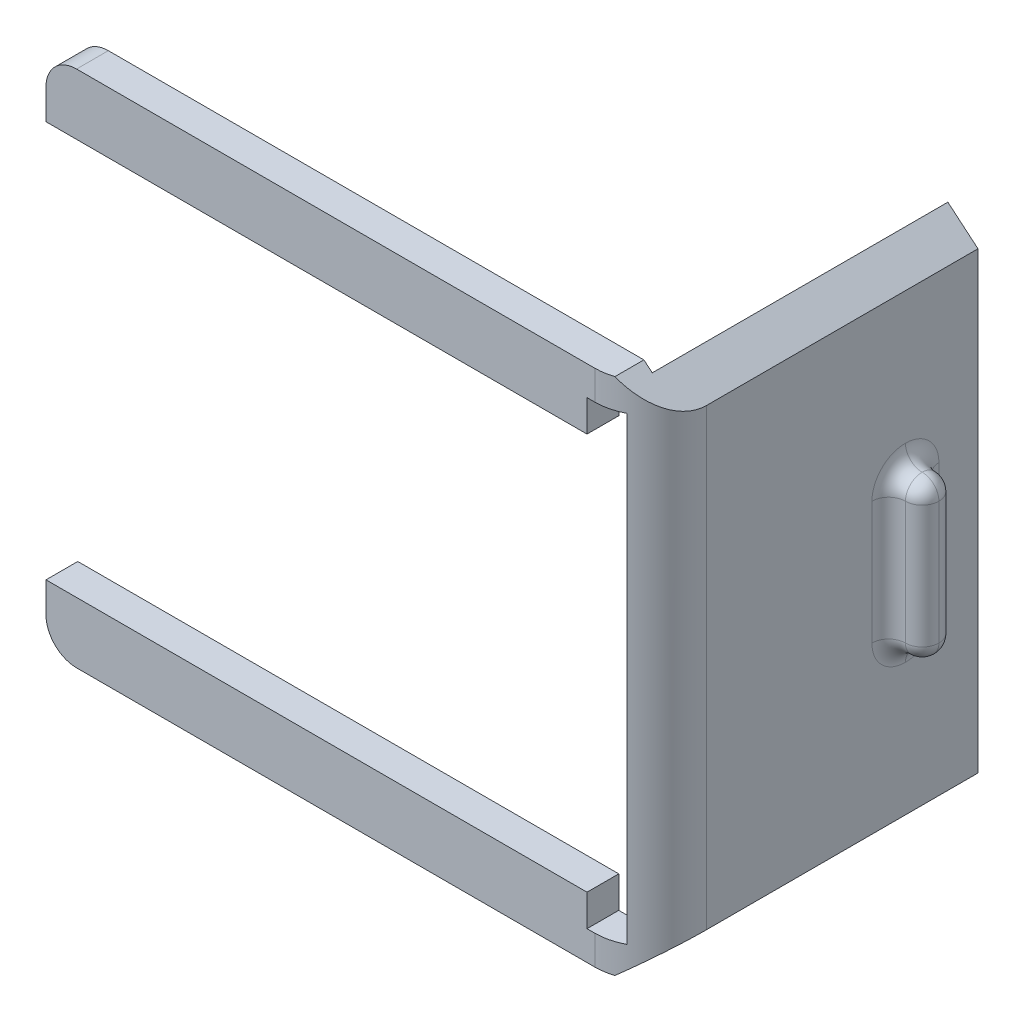
SolidWorks part; units mm, degrees
ref_plane "Front Plane" through (0, 0, 0) normal (0, 0, 1) x (1, 0, 0)
ref_plane "Top Plane" through (0, 0, 0) normal (0, 1, 0) x (1, 0, 0)
ref_plane "Right Plane" through (0, 0, 0) normal (1, 0, 0) x (0, 0, -1)
sketch "Sketch1" plane through (0, 0, 0) normal (0, 0, 1) x (1, 0, 0)
  line L5 (33.75, 21.7751) -> (33.75, 19.7751) construction
  line L6 (36.75, 19.2578) -> (33.75, 21.7751) construction
  line L10 (36.649, -1.25) -> (33.95, -1.25) construction
  line L11 (36.649, -21.8426) -> (36.649, 19.3426) construction
  line L14 (33.95, 21.3462) -> (33.95, -23.8462)
  line L15 (36.649, 19.0815) -> (33.95, 21.3462)
  line L16 (36.649, 19.0815) -> (36.649, -1.25)
  line L17 (36.649, -21.5815) -> (33.95, -23.8462)
  line L18 (36.649, -21.5815) -> (36.649, -1.25)
  line L19 (36.75, -21.7578) -> (33.2733, -24.6751) construction
  dimension "D2" = 0.2
  dimension "D1" = 0.2
extrude "Boss-Extrude1" add sketch "Sketch1" along normal up to vertex (28.8084 mm away)
sketch "Sketch2" plane through (0, 0, 29.3184) normal (0, 0, 1) x (1, 0, 0)
  line L0 (33.95, -21.8462) -> (33.95, -23.8462)
  line L1 (33.95, -1.25) -> (-17.704, -1.25) construction
  line L5 (-17.5037, -21.7351) -> (-17.5037, -19.0141)
  line L7 (33.95, -23.8462) -> (33.2005, -24.4751)
  line L8 (33.2005, -24.4751) -> (-14.764, -24.4751)
  line L9 (33.2733, -24.6751) -> (-14.764, -24.6751) construction
  line L10 (33.95, -23.8462) -> (36.649, -21.5815) construction
  line L11 (-17.5037, -19.0141) -> (30.95, -19.0141)
  line L12 (30.95, -19.0141) -> (30.95, -21.8462)
  line L13 (30.95, -21.8462) -> (33.95, -21.8462)
  line L14 (33.95, 21.3462) -> (33.95, -23.8462) construction
  line L15 (-16.2626, -18.8141) -> (29.6606, -18.8141) construction
  line L16 (-17.704, 19.2351) -> (-17.704, -21.7351) construction
  line L17 (30.95, 19.3462) -> (33.95, 19.3462)
  line L18 (30.95, 16.5141) -> (30.95, 19.3462)
  line L19 (-17.5037, 16.5141) -> (30.95, 16.5141)
  line L20 (-17.5037, 19.2351) -> (-17.5037, 16.5141)
  line L21 (33.2005, 21.9751) -> (-14.764, 21.9751)
  line L22 (33.95, 21.3462) -> (33.2005, 21.9751)
  line L23 (33.95, 19.3462) -> (33.95, 21.3462)
  arc A0 (-14.764, -24.4751) -> (-17.5037, -21.7351) centre (-14.764, -21.7354) cw
  arc A2 (-14.764, 21.9751) -> (-17.5037, 19.2351) centre (-14.764, 19.2354) ccw
  dimension "D2" = 2.7397
  dimension "D3" = 0.2
  dimension "D4" = 2
  dimension "D5" = 3
  dimension "D6" = 0.2
extrude "Boss-Extrude2" add sketch "Sketch2" against normal up to surface (2.8448 mm away) contours L17 L23 L22 L21 A2 L20 L19 L18 | L0 L7 L8 A0 L5 L11 L12 L13
fillet "Fillet1" radius 5 1 edges at (36.649, -1.25, 29.3184)
sketch "Sketch3" plane through (36.649, 0, 0) normal (1, 0, 0) x (0, 0, -1)
  line L0 (0, -1.25) -> (-24.7972, -1.25) construction
  line L1 (-8, -8.25) -> (-5, -8.25)
  line L2 (-8, -8.25) -> (-8, 5.75)
  line L3 (-8, 5.75) -> (-5, 5.75)
  line L4 (-5, -8.25) -> (-5, 5.75)
  line L5 (0, -21.5815) -> (0, 19.0815) construction
  point P9 (-5, -1.25)
  dimension "D1" = 14
  dimension "D2" = 3
  dimension "D3" = 5
extrude "Boss-Extrude3" add sketch "Sketch3" along normal blind 3
fillet "Fillet2" radius 1.5 4 edges at (39.649, 5.75, 6.5) (39.649, -1.25, 5) (39.649, -8.25, 6.5) (39.649, -1.25, 8)
fillet "Fillet3" radius 1.5 6 edges at (36.649, -1.25, 8) (36.649, -1.25, 5) (39.2096, 5.3107, 5.4393) (39.2096, 5.3107, 7.5607) (39.2096, -7.8107, 7.5607) (39.2096, -7.8107, 5.4393)
